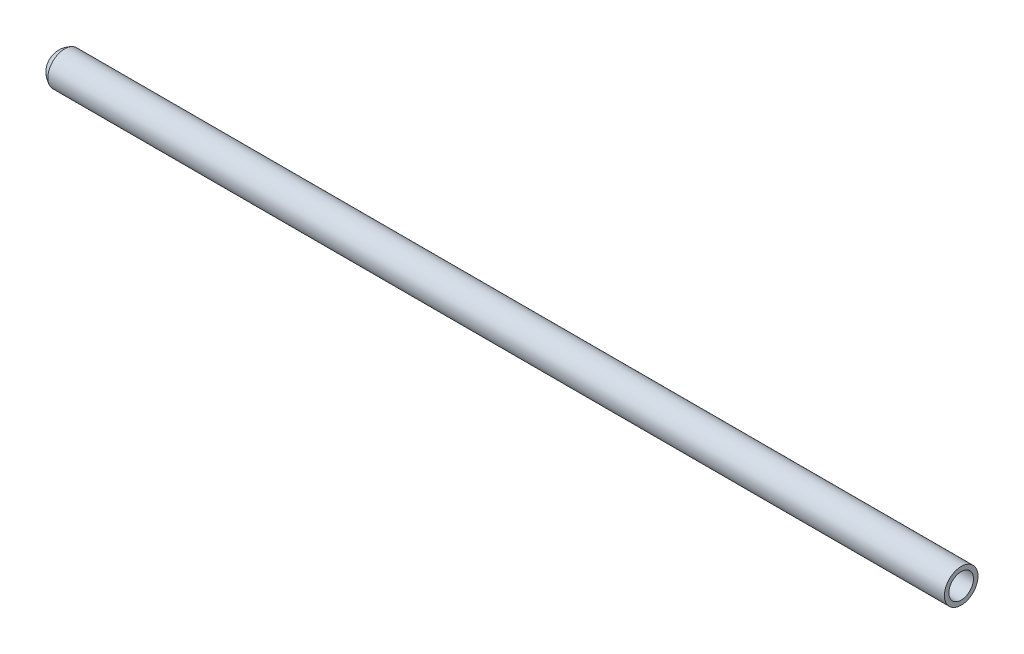
SolidWorks part; units mm, degrees
material "S-Glass Fiber"
ref_plane "Front Plane" through (0, 0, 0) normal (0, 0, 1) x (1, 0, 0)
ref_plane "Top Plane" through (0, 0, 0) normal (0, 1, 0) x (1, 0, 0)
ref_plane "Right Plane" through (0, 0, 0) normal (1, 0, 0) x (0, 0, -1)
sketch "Sketch1" plane through (0, 0, 0) normal (1, 0, 0) x (0, 0, -1)
  circle A0 centre (0, 0) radius 9.525
  dimension "D1" = 19.05
extrude "Boss-Extrude1" add sketch "Sketch1" against normal blind 508
dome "Dome1" faces to dome 1 distance 6.35 reverse direction no elliptical dome no face at (-508, 0, -9.525) parameters "D1"=6.35
shell "Shell1" thickness 2.54 removed face at (0, 0, -9.525)
